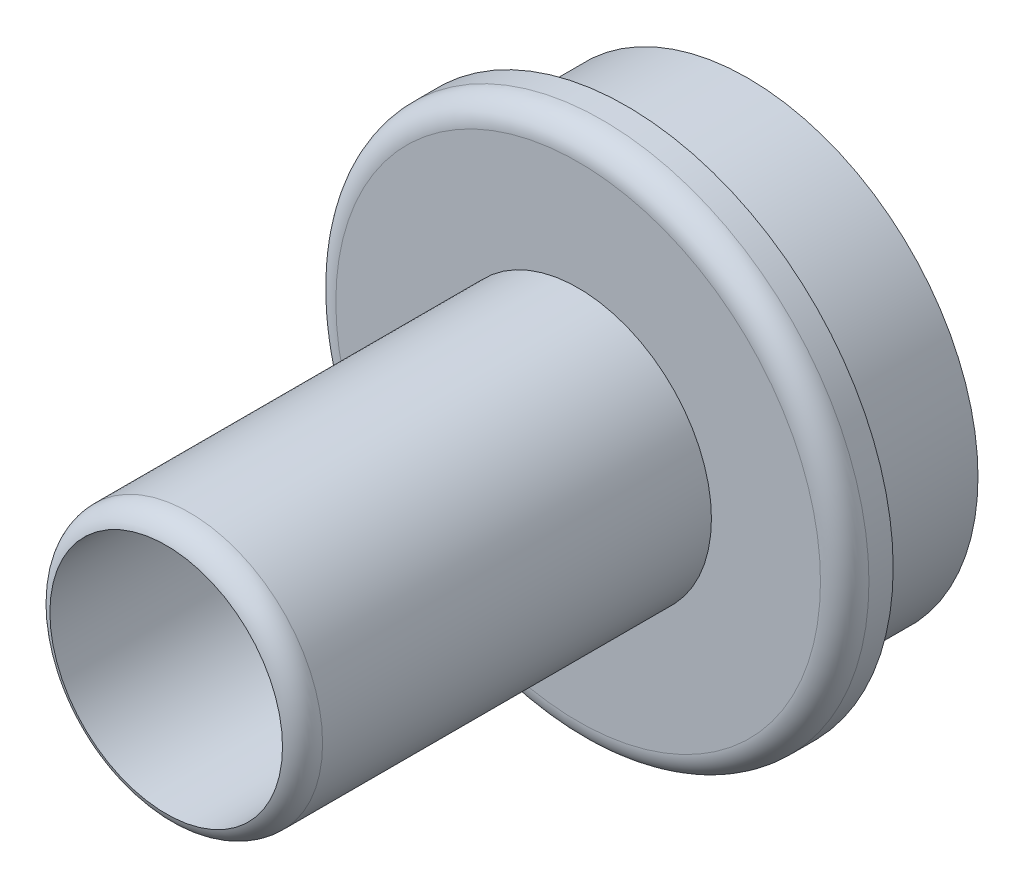
SolidWorks part; units mm, degrees
ref_plane "Front Plane" through (0, 0, 0) normal (0, 0, 1) x (1, 0, 0)
ref_plane "Top Plane" through (0, 0, 0) normal (0, 1, 0) x (1, 0, 0)
ref_plane "Right Plane" through (0, 0, 0) normal (1, 0, 0) x (0, 0, -1)
sketch "Sketch1" plane through (0, 0, 0) normal (0, 0, 1) x (1, 0, 0)
  circle A0 centre (0, 0) radius 11
extrude "Boss-Extrude1" add sketch "Sketch1" along normal blind 2 contours A0
sketch "Sketch2" plane through (0, 0, 0) normal (0, 0, -1) x (-1, 0, 0)
  circle A0 centre (0, 0) radius 9.5
extrude "Boss-Extrude2" add sketch "Sketch2" along normal blind 5
sketch "Sketch3" plane through (0, 0, 2) normal (0, 0, 1) x (1, 0, 0)
  circle A0 centre (0, 0) radius 5.5
extrude "Boss-Extrude3" add sketch "Sketch3" along normal blind 17 contours A0
sketch "Sketch4" plane through (0, 0, 19) normal (0, 0, 1) x (1, 0, 0)
  circle A0 centre (0, 0) radius 4.8
extrude "Cut-Extrude1" cut sketch "Sketch4" against normal blind 25 contours A0
sketch "Sketch5" plane through (0, 0, -5) normal (0, 0, -1) x (-1, 0, 0)
  circle A0 centre (0, 0) radius 8.8
extrude "Cut-Extrude2" cut sketch "Sketch5" against normal blind 5.5 contours A0
fillet "Fillet1" radius 2 1 edges at (-4.8, 0, 0.5)
fillet "Fillet2" radius 1 1 edges at (11, 0, 2)
fillet "Fillet3" radius 1 1 edges at (5.5, 0, 19)
